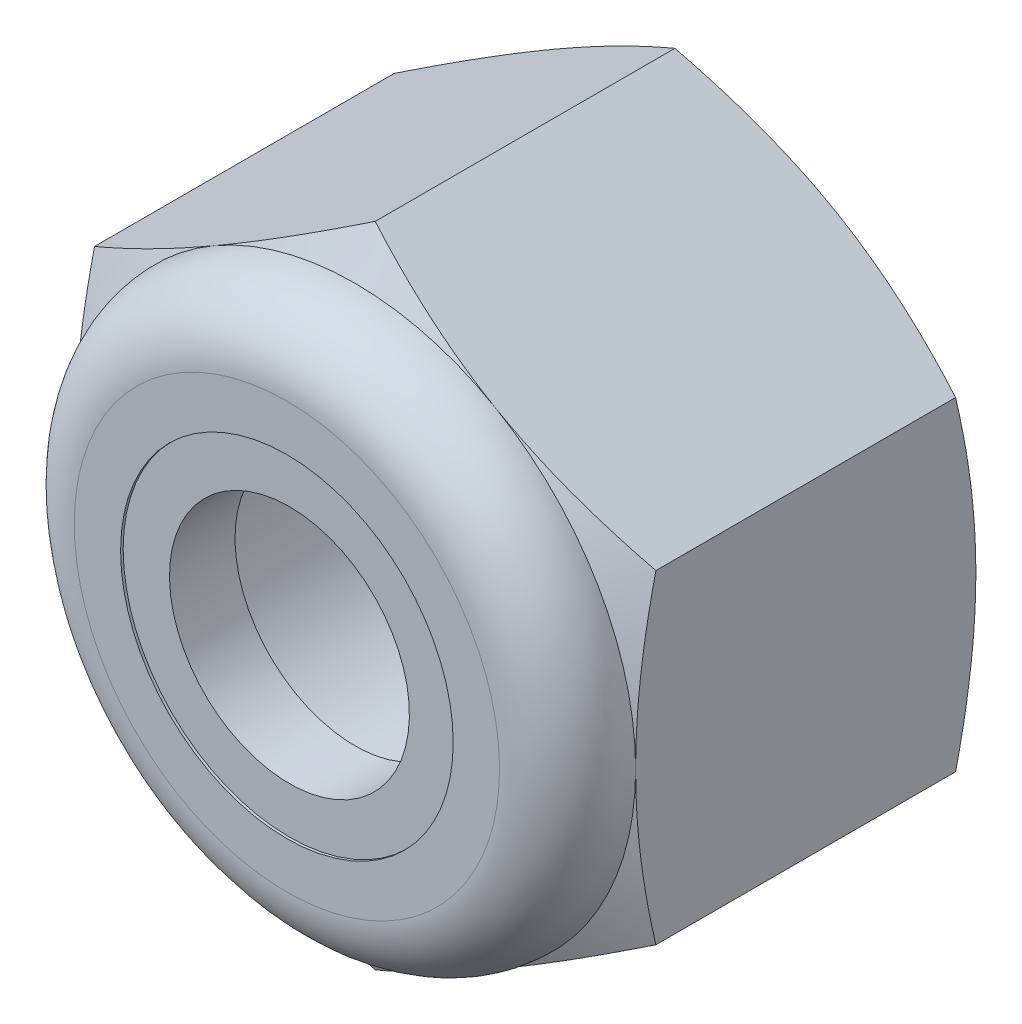
SolidWorks part; units mm, degrees
material "Alloy Steel"
ref_plane "Front Plane" through (0, 0, 0) normal (0, 0, 1) x (1, 0, 0)
ref_plane "Top Plane" through (0, 0, 0) normal (0, 1, 0) x (1, 0, 0)
ref_plane "Right Plane" through (0, 0, 0) normal (1, 0, 0) x (0, 0, -1)
ref_axis "Central Axis" through (0, 0, -89.0857) along (0, 0, 1)
sketch "Sketch1" plane through (0, 0, 0) normal (0, 0, 1) x (1, 0, 0)
  line L1 (0, 3.1754) -> (-2.75, 1.5877)
  line L2 (-2.75, 1.5877) -> (-2.75, -1.5877)
  line L3 (-2.75, -1.5877) -> (0, -3.1754)
  line L4 (0, -3.1754) -> (2.75, -1.5877)
  line L5 (2.75, -1.5877) -> (2.75, 1.5877)
  line L6 (2.75, 1.5877) -> (0, 3.1754)
  circle A0 centre (0, 0) radius 2.75 construction
  circle A1 centre (0, 0) radius 1.5
  point P10 (0, -1.5)
  point P11 (0, 1.5)
  point P12 (0, 2.75)
  dimension "Thread Size" = 3
  dimension "Width" = 5.5
sketch "Sketch2" plane through (0, 0, 0) normal (1, 0, 0) x (0, 0, -1)
  line L0 (2, 0) -> (-2, 0) construction
  line L1 (-2, 1.5) -> (2, 1.5) construction
  line L2 (-1.975, -1.6293) -> (-3.27, -1.6293) construction
  line L3 (-2.4688, 1.5541) -> (-1.9688, 1.5541) construction
  line L4 (-1.9688, 1.5541) -> (-2.2188, 1.1211) construction
  line L5 (-2.2188, 1.1211) -> (-2.4688, 1.5541) construction
  line L6 (-2.4375, 1.5) -> (-2, 1.5) construction
  line L7 (-2.25, 1.1752) -> (-2.1875, 1.1752) construction
  line L8 (-2.2188, 1.1752) -> (-2.2188, 1.1211) construction
  line L9 (-2.2188, 1.5) -> (-2.2188, 1.5541) construction
  line L10 (-1.9844, 1.5271) -> (-2.4531, 1.5271)
  line L11 (-2.4531, 1.5271) -> (-2.25, 1.1752)
  line L12 (-2.25, 1.1752) -> (-2.1875, 1.1752)
  line L13 (-2.1875, 1.1752) -> (-1.9844, 1.5271)
  line L14 (2, 0) -> (3.27, 0)
  line L15 (3.27, 0) -> (3.27, 4.4454)
  line L16 (0, 4.4454) -> (0, 3.1754) construction
  line L17 (0, 3.1754) -> (0, 1.5877) construction
  line L18 (2, 2.75) -> (-1.3333, 2.75) construction
  line L19 (-2.25, -1.1752) -> (-2.1875, -1.1752) construction
  line L20 (2, 2.75) -> (2, 0)
  line L21 (1.8016, 3.1754) -> (-1.135, 3.1754)
  line L22 (2, 2.75) -> (1.8016, 3.1754)
  line L23 (-2, 0) -> (-2, 2.0833) construction
  line L24 (-1.3333, 2.75) -> (-1.135, 3.1754)
  line L25 (3.27, 4.4454) -> (-3.27, 4.4454)
  line L26 (-2, 2.0833) -> (-3.27, 2.0833)
  line L27 (-3.27, 2.0833) -> (-3.27, 4.4454)
  line L28 (-1.975, 2.0833) -> (-1.975, 1.1752) construction
  line L29 (-1.975, 1.6293) -> (-3.27, 1.6293)
  line L30 (-3.27, 1.6293) -> (-3.27, 0)
  line L31 (-3.27, 0) -> (-1.3333, 0)
  line L32 (-1.3333, 0) -> (-1.3333, 2.725)
  line L33 (-1.975, 1.6293) -> (-1.975, 2.0833)
  arc A0 (-1.3333, 2.75) -> (-2, 2.0833) centre (-1.3333, 2.0833) ccw
  arc A1 (-1.3333, 2.725) -> (-1.975, 2.0833) centre (-1.3333, 2.0833) ccw
  point P4 (0, 0)
  point P18 (-2.2188, 1.5271)
  point P22 (-2.2188, 1.5271)
  point P33 (0, 3.1754)
  point P48 (-3.27, -1.6293)
  point P51 (-2.25, -1.1752)
  dimension "Height" = 4
  dimension "Pitch" = 0.5
  dimension "D1" = 0.0625
  dimension "D2" = 1.27
  dimension "D3" = 25
  dimension "D4" = 0.6667
  dimension "D5" = 25
  dimension "D6" = 0.025
sketch "Sketch3" plane through (0, 0, 0) normal (0, 0, 1) x (1, 0, 0)
  line L0 (0, -3.1754) -> (2.75, -1.5877) construction
  line L1 (2.75, -1.5877) -> (2.75, 1.5877) construction
  line L2 (2.75, 1.5877) -> (0, 3.1754) construction
  line L3 (0, 3.1754) -> (-2.75, 1.5877) construction
  line L4 (-2.75, 1.5877) -> (-2.75, -1.5877) construction
  line L5 (-2.75, -1.5877) -> (0, -3.1754) construction
  line L6 (0, -3.1754) -> (2.75, -1.5877)
  line L7 (2.75, -1.5877) -> (2.75, 1.5877)
  line L8 (2.75, 1.5877) -> (0, 3.1754)
  line L9 (0, 3.1754) -> (-2.75, 1.5877)
  line L10 (-2.75, 1.5877) -> (-2.75, -1.5877)
  line L11 (-2.75, -1.5877) -> (0, -3.1754)
  circle A0 centre (0, 0) radius 1.5 construction
  circle A1 centre (0, 0) radius 1.5
extrude "Boss-Extrude1" add sketch "Sketch3" along normal mid plane 4
sketch "Sketch4" plane through (0, 0, 0) normal (1, 0, 0) x (0, 0, -1)
  line L0 (3.27, 4.4454) -> (-3.27, 4.4454) construction
  line L1 (-3.27, 2.0833) -> (-3.27, 4.4454) construction
  line L2 (-2, 2.0833) -> (-3.27, 2.0833) construction
  line L3 (-1.3333, 2.75) -> (-1.135, 3.1754) construction
  line L4 (1.8016, 3.1754) -> (-1.135, 3.1754) construction
  line L5 (2, 2.75) -> (1.8016, 3.1754) construction
  line L6 (2, 2.75) -> (2, 0) construction
  line L7 (2, 0) -> (3.27, 0) construction
  line L8 (3.27, 0) -> (3.27, 4.4454) construction
  line L9 (-3.27, 1.6293) -> (-3.27, 0) construction
  line L10 (-3.27, 0) -> (-1.3333, 0) construction
  line L11 (-1.3333, 0) -> (-1.3333, 2.725) construction
  line L12 (-1.975, 1.6293) -> (-1.975, 2.0833) construction
  line L13 (-1.975, 1.6293) -> (-3.27, 1.6293) construction
  line L14 (3.27, 4.4454) -> (-3.27, 4.4454)
  line L15 (-3.27, 2.0833) -> (-3.27, 4.4454)
  line L16 (-2, 2.0833) -> (-3.27, 2.0833)
  line L17 (-1.3333, 2.75) -> (-1.135, 3.1754)
  line L18 (1.8016, 3.1754) -> (-1.135, 3.1754)
  line L19 (2, 2.75) -> (1.8016, 3.1754)
  line L20 (2, 2.75) -> (2, 0)
  line L21 (2, 0) -> (3.27, 0)
  line L22 (3.27, 0) -> (3.27, 4.4454)
  line L23 (-3.27, 1.6293) -> (-3.27, 0)
  line L24 (-3.27, 0) -> (-1.3333, 0)
  line L25 (-1.3333, 0) -> (-1.3333, 2.725)
  line L26 (-1.975, 1.6293) -> (-1.975, 2.0833)
  line L27 (-1.975, 1.6293) -> (-3.27, 1.6293)
  arc A0 (-1.3333, 2.75) -> (-2, 2.0833) centre (-1.3333, 2.0833) ccw construction
  arc A1 (-1.3333, 2.725) -> (-1.975, 2.0833) centre (-1.3333, 2.0833) ccw construction
  arc A2 (-1.3333, 2.75) -> (-2, 2.0833) centre (-1.3333, 2.0833) ccw
  arc A3 (-1.3333, 2.725) -> (-1.975, 2.0833) centre (-1.3333, 2.0833) ccw
revolve "Cut-Revolve1" cut sketch "Sketch4" angle 360 about L0
sketch "Sketch5" plane through (0, 0, 0) normal (1, 0, 0) x (0, 0, -1)
  line L0 (-1.975, 2.0833) -> (-1.975, 1.1752) construction
  line L1 (-1.3333, 0) -> (-1.3333, 2.725) construction
  line L2 (-1.975, 2.0833) -> (-1.975, 1.1752)
  line L3 (-1.3333, 1.1752) -> (-1.3333, 2.725)
  line L4 (-1.975, 1.1752) -> (-1.3333, 1.1752)
  arc A0 (-1.3333, 2.725) -> (-1.975, 2.0833) centre (-1.3333, 2.0833) ccw construction
  arc A1 (-1.3333, 2.725) -> (-1.975, 2.0833) centre (-1.3333, 2.0833) ccw
revolve "Revolve1" add sketch "Sketch5" angle 360 about L0
sketch "Sketch6" [suppressed] plane through (0, 0, 2) normal (0, 0, 1) x (1, 0, 0)
  circle A0 centre (0, 0) radius 1.5 construction
  circle A1 centre (0, 0) radius 1.5
curve "Helix/Spiral1" [suppressed] pitch 0.5 height 4.5 turns 9
sketch "Sketch7" [suppressed] plane through (0, 0, 0) normal (1, 0, 0) x (0, 0, -1)
  line L0 (-2.4531, 1.5271) -> (-2.25, 1.1752) construction
  line L1 (-2.25, 1.1752) -> (-2.1875, 1.1752) construction
  line L2 (-2.1875, 1.1752) -> (-1.9844, 1.5271) construction
  line L3 (-1.9844, 1.5271) -> (-2.4531, 1.5271) construction
  line L4 (-2.4531, 1.5271) -> (-2.25, 1.1752)
  line L5 (-2.25, 1.1752) -> (-2.1875, 1.1752)
  line L6 (-2.1875, 1.1752) -> (-1.9844, 1.5271)
  line L7 (-1.9844, 1.5271) -> (-2.4531, 1.5271)
sweep "Sweep1" [suppressed] add profiles "Sketch7" path "Helix/Spiral1"
sketch "Sketch8" [suppressed] plane through (0, 0, -2) normal (0, 0, -1) x (-1, 0, 0)
  circle A2 centre (0, 0) radius 1.5271
  point P2 (0, 1.5271)
extrude "Cut-Extrude1" [suppressed] cut sketch "Sketch8" along normal through all and the other way through all draft 60
sketch "Sketch9" [suppressed] plane through (0, 0, 1.3333) normal (0, 0, 1) x (1, 0, 0)
  circle A2 centre (0, 0) radius 1.5271
  circle A3 centre (0, 0) radius 1.1752 construction
  point P2 (0, 1.5271)
  point P4 (0, 1.1752)
extrude "Cut-Extrude2" [suppressed] cut sketch "Sketch9" along normal through all and the other way through all draft 60
equation "\"D1@Sketch2\" = \"Pitch@Sketch2\" / 8"
equation "\"D4@Sketch2\"=\"Height@Sketch2\"/6"
equation "\"D1@Boss-Extrude1\"=\"Height@Sketch2\""
equation "\"D3@Helix/Spiral1\"=\"Height@Sketch2\"+\"Pitch@Sketch2\""
equation "\"D4@Helix/Spiral1\"=\"Pitch@Sketch2\""
equation "\"D6@Sketch2\"=\"Pitch@Sketch2\"*0.05"
